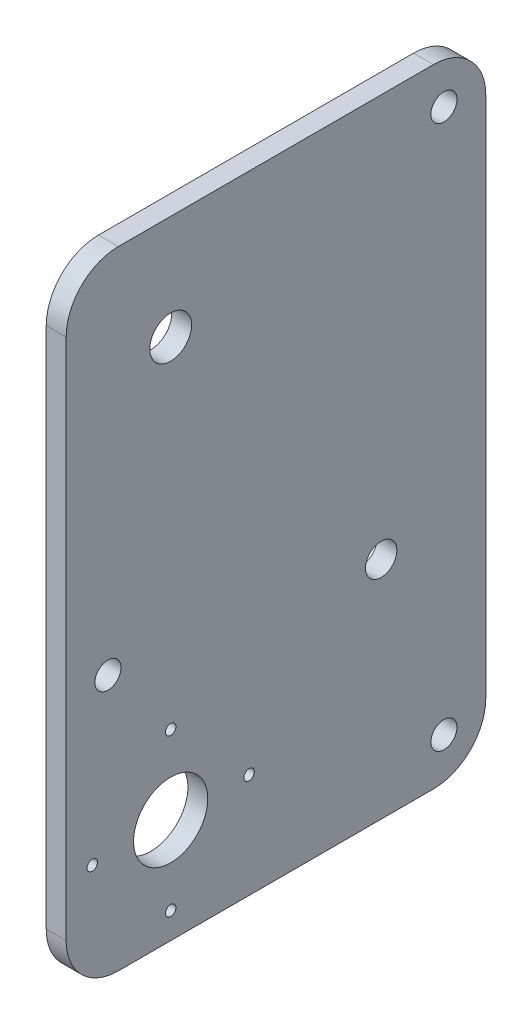
SolidWorks part; units mm, degrees
ref_plane "Front Plane" through (0, 0, 0) normal (0, 0, 1) x (1, 0, 0)
ref_plane "Top Plane" through (0, 0, 0) normal (0, 1, 0) x (1, 0, 0)
ref_plane "Right Plane" through (0, 0, 0) normal (1, 0, 0) x (0, 0, -1)
sketch "Sketch1" plane through (0, 0, 0) normal (1, 0, 0) x (0, 0, -1)
  line L0 (2.0601, -18.4136) -> (2.0601, -98.4136) construction
  line L5 (2.0601, -75.3642) -> (42.3302, -75.3642) construction
  line L6 (-17.9399, -68.4136) -> (-9.9399, -68.4136) construction
  line L7 (-17.9399, 1.5864) -> (62.3302, 1.5864)
  line L8 (-17.9399, 1.5864) -> (-17.9399, -118.4136)
  line L9 (-17.9399, -118.4136) -> (62.3302, -118.4136)
  line L10 (62.3302, 1.5864) -> (62.3302, -118.4136)
  line L13 (-17.9399, -58.4136) -> (62.3302, -58.4136) construction
  circle A0 centre (2.0601, -18.4136) radius 4
  circle A1 centre (2.0601, -98.4136) radius 7.1
  circle A3 centre (42.3302, -75.3642) radius 3
  circle A4 centre (2.0601, -98.4136) radius 17.9 construction
  circle A5 centre (2.0601, -18.4136) radius 41.25 construction
  circle A6 centre (42.3302, -75.3642) radius 28.5 construction
  circle A7 centre (2.0601, -98.4136) radius 15 construction
  circle A8 centre (2.0601, -83.4136) radius 1
  circle A9 centre (17.0601, -98.4136) radius 1
  circle A10 centre (2.0601, -113.4136) radius 1
  circle A11 centre (-12.9399, -98.4136) radius 1
  circle A14 centre (54.3302, -6.4136) radius 2.5
  circle A16 centre (54.3302, -110.4136) radius 2.5
  circle A17 centre (-9.9399, -68.4136) radius 2.5
  point P5 (-13.9399, -68.4136)
  point P27 (2.0601, -98.4136)
  dimension "D2" = 8
  dimension "D3" = 14.2
  dimension "D6" = 6
  dimension "D1" = 82.5
  dimension "D4" = 35.8
  dimension "D5" = 57
  dimension "D7" = 80
  dimension "D12" = 4
  dimension "D13" = 8
  dimension "D8" = 20
  dimension "D9" = 20
  dimension "D10" = 20
  dimension "D11" = 20
  dimension "D14" = 8
  dimension "D15" = 10
  dimension "D16" = 8
extrude "Boss-Extrude1" add sketch "Sketch1" along normal blind 3.8
fillet "Fillet1" radius 10 4 edges at (1.9, 1.5864, 17.9399) (1.9, 1.5864, -62.3302) (1.9, -118.4136, -62.3302) (1.9, -118.4136, 17.9399)
